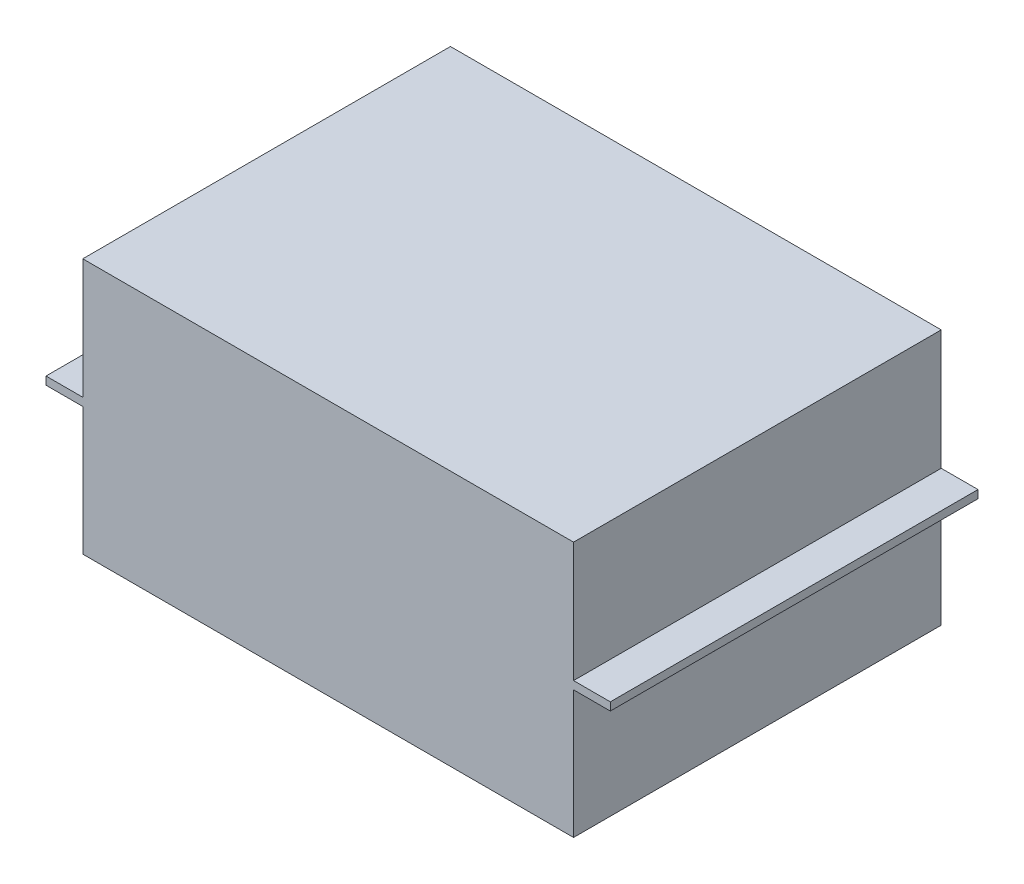
SolidWorks part; units mm, degrees
ref_plane "Front Plane" through (0, 0, 0) normal (0, 0, 1) x (1, 0, 0)
ref_plane "Top Plane" through (0, 0, 0) normal (0, 1, 0) x (1, 0, 0)
ref_plane "Right Plane" through (0, 0, 0) normal (1, 0, 0) x (0, 0, -1)
sketch "Sketch1" plane through (0, 0, 0) normal (0, 1, 0) x (1, 0, 0)
  line L1 (-153.5, -115) -> (153.5, -115)
  line L2 (-153.5, -115) -> (-153.5, 115)
  line L3 (-153.5, 115) -> (153.5, 115)
  line L4 (153.5, -115) -> (153.5, 115)
  line L5 (-153.5, -115) -> (153.5, 115) construction
  line L6 (-153.5, 115) -> (153.5, -115) construction
  line L7 (-176.5, -115) -> (176.5, -115)
  line L8 (-176.5, -115) -> (-176.5, 115)
  line L9 (-176.5, 115) -> (176.5, 115)
  line L10 (176.5, -115) -> (176.5, 115)
  line L11 (-176.5, -115) -> (176.5, 115) construction
  line L12 (-176.5, 115) -> (176.5, -115) construction
  point P0 (0, 0)
  point P6 (0, 0)
  dimension "D1" = 307
  dimension "D2" = 230
  dimension "D3" = 353
extrude "Boss-Extrude1" add sketch "Sketch1" along normal blind 160 contours L1 L4 L3 L2 region at (0, 0, 0)
extrude "Boss-Extrude2" add sketch "Sketch1<3>" along normal blind 5 from offset 80 contours L9 L8 L7 L2 | L7 L10 L9 L4 region at (-165, 0, 0) region at (165, 0, 0)
sketch "Sketch1<3>" plane through (0, 0, 0) normal (0, 1, 0) x (1, 0, 0) same geometry as "Sketch1"
sketch "Sketch2" plane through (0, 85, 0) normal (0, 1, 0) x (1, 0, 0)
  line L0 (176.5, -115) -> (176.5, 115) construction
  line L1 (161, -4) -> (169, -4)
  line L3 (161, 4) -> (169, 4)
  line L7 (153.5, 115) -> (176.5, 115) construction
  line L8 (165, 4) -> (165, -4) construction
  ellipse E0 centre (161, 0) end of major axis (161, 4) minor radius 3.5 (161, -4) -> (161, 4) cw
  ellipse E1 centre (169, 0) end of major axis (169, 4) minor radius 3.5 (169, -4) -> (169, 4) ccw
  point P0 (0, 0)
  point P8 (176.5, 0)
  point P11 (165, 115)
  point P23 (169, 4)
  point P24 (0, 0)
  point P25 (0, 0)
  point P26 (0, 0)
  point P27 (0, 0)
  point P28 (0, 0)
  point P29 (0, 0)
  dimension "D2" = 11.5
  dimension "D1" = 8
  dimension "D3" = 15
  dimension "D4" = 4
